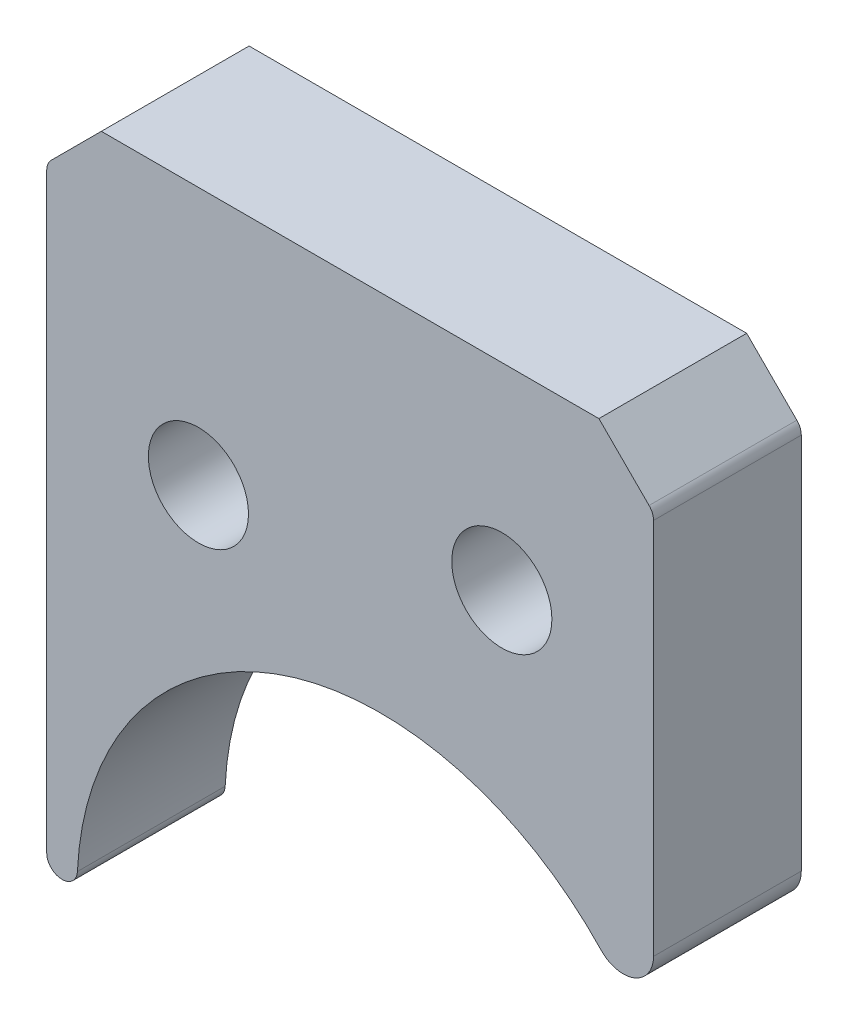
SolidWorks part; units mm, degrees
ref_plane "Front Plane" through (0, 0, 0) normal (0, 0, 1) x (1, 0, 0)
ref_plane "Top Plane" through (0, 0, 0) normal (0, 1, 0) x (1, 0, 0)
ref_plane "Right Plane" through (0, 0, 0) normal (1, 0, 0) x (0, 0, -1)
sketch "Sketch1" plane through (0, 0, 0) normal (0, 0, 1) x (1, 0, 0)
  line L0 (0, 22) -> (20, 22)
  line L1 (0, 0) -> (1, 0)
  line L2 (0, 0) -> (0, 22)
  line L4 (20, 4.3589) -> (20, 22)
  arc A0 (20, 4.3589) -> (1, 0) centre (11, 0) ccw
  dimension "D1" = 17.6411
  dimension "D2" = 22
extrude "Boss-Extrude1" add sketch "Sketch1" along normal blind 4.87
sketch "Sketch2" plane through (0, 0, 4.87) normal (0, 0, 1) x (1, 0, 0)
  line L0 (5, 15.5) -> (11, 15.5) construction
  line L1 (11, 15.5) -> (15, 15.5) construction
  line L2 (11, 15.5) -> (11, 0) construction
  line L3 (5, 15.5) -> (5, 13.5) construction
  circle A0 centre (5, 13.5) radius 1.65
  circle A1 centre (15, 15.5) radius 1.65
  dimension "D5" = 15.5
  dimension "D4" = 3.3
  dimension "D1" = 11
  dimension "D2" = 6
  dimension "D3" = 2
  dimension "D6" = 4
extrude "Cut-Extrude1" cut sketch "Sketch2" against normal blind 4.87
chamfer "Chamfer1" distance 1.8 angle 45 2 edges at (20, 22, 2.435) (0, 22, 2.435)
fillet "Fillet1" radius 0.5 4 edges at (0, 0, 2.435) (1, 0, 2.435) (0, 20.2, 2.435) (20, 20.2, 2.435)
fillet "Fillet2" radius 1 1 edges at (20, 4.3589, 2.435)
